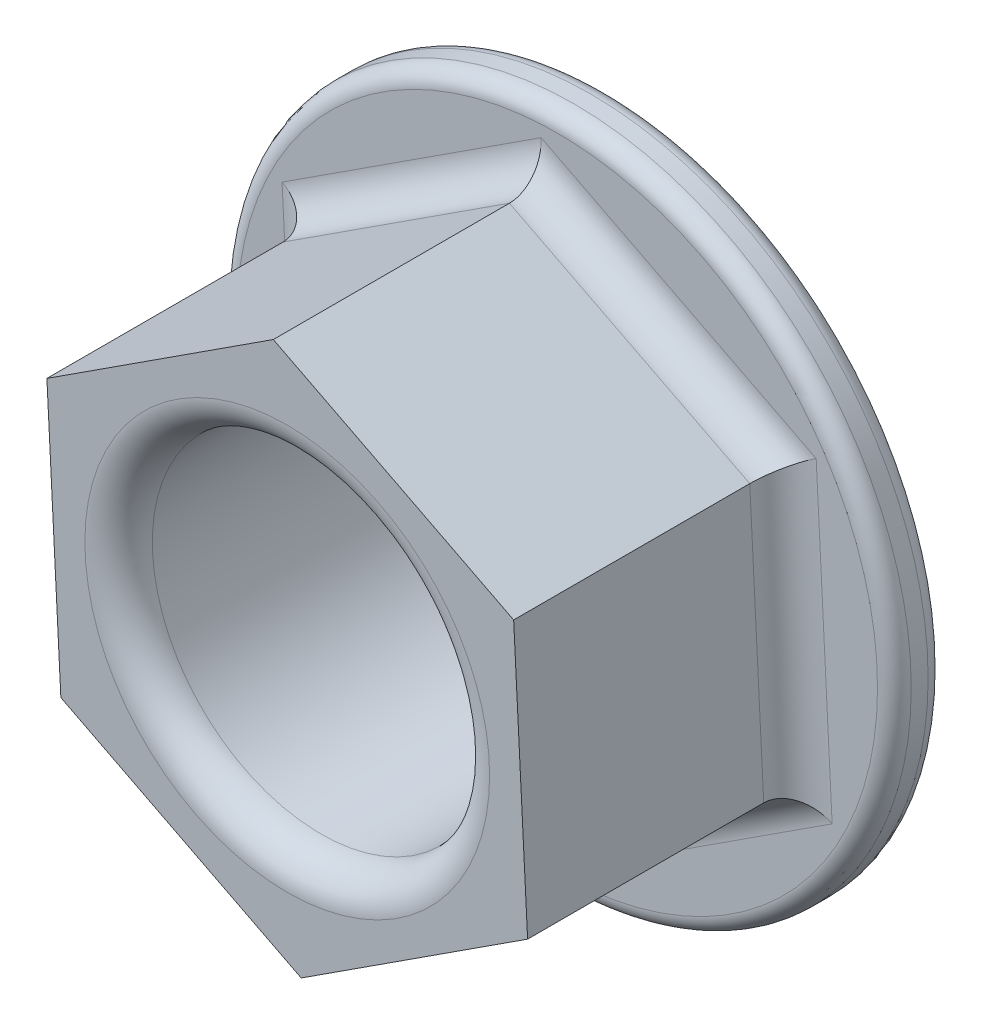
SolidWorks part; units mm, degrees
ref_plane "Front Plane" through (0, 0, 0) normal (0, 0, 1) x (1, 0, 0)
ref_plane "Top Plane" through (0, 0, 0) normal (0, 1, 0) x (1, 0, 0)
ref_plane "Right Plane" through (0, 0, 0) normal (1, 0, 0) x (0, 0, -1)
sketch "Sketch1" plane through (0, 0, 0) normal (0, 0, 1) x (1, 0, 0)
  circle A0 centre (0, 0) radius 10
  dimension "D1" = 20
extrude "Boss-Extrude2" add sketch "Sketch1" along normal blind 1.5
fillet "Fillet1" radius 0.5 2 edges at (10, 0, 0) (10, 0, 1.5)
sketch "Sketch3" plane through (0, 0, 1.5) normal (0, 0, 1) x (1, 0, 0)
  line L1 (-7.1259, 3.6362) -> (-6.712, -4.3531)
  line L2 (-6.712, -4.3531) -> (0.4139, -7.9893)
  line L3 (0.4139, -7.9893) -> (7.1259, -3.6362)
  line L4 (7.1259, -3.6362) -> (6.712, 4.3531)
  line L5 (6.712, 4.3531) -> (-0.4139, 7.9893)
  line L6 (-0.4139, 7.9893) -> (-7.1259, 3.6362)
  circle A0 centre (0, 0) radius 6.9282 construction
  dimension "D1" = 8
extrude "Boss-Extrude3" add sketch "Sketch3" along normal blind 8
fillet "Fillet2" radius 1 6 edges at (-3.149, -6.1712, 1.5) (-6.9189, -0.3585, 1.5) (-3.7699, 5.8127, 1.5) (3.149, 6.1712, 1.5) (6.9189, 0.3585, 1.5) (3.7699, -5.8127, 1.5)
sketch "Sketch5" plane through (0, 0, 9.5) normal (0, 0, 1) x (1, 0, 0)
  circle A0 centre (0, 0) radius 5
  dimension "D1" = 10
extrude "Cut-Extrude1" cut sketch "Sketch5" against normal through all contours A0
sketch "Sketch6" plane through (0, 0, 9.5) normal (0, 0, 1) x (1, 0, 0)
  circle A0 centre (0, 0) radius 5 construction
  circle A1 centre (0, 0) radius 5
curve "Helix/Spiral1" pitch 0.5 height 10 turns 20
sketch3d "3DSketch1"
  circle A0 centre (4.0448, -2.9388, -0.3) radius 0.0335
  spline S0 degree 3 poles (-5, 0, 9.5) (-5, 0.6503, 9.4897) (-4.7397, 1.9651, 9.4687) (-3.6276, 3.6271, 9.4375) (-1.9632, 4.7398, 9.4062) (0, 5.1301, 9.375) (1.9632, 4.7397, 9.3437) (3.6276, 3.6276, 9.3125) (4.7397, 1.9632, 9.2812) (5.1302, 0, 9.25) (4.7397, -1.9632, 9.2187) (3.6276, -3.6276, 9.1875) (1.9632, -4.7397, 9.1562) (0, -5.1302, 9.125) (-1.9632, -4.7397, 9.0937) (-3.6276, -3.6276, 9.0625) (-4.7397, -1.9632, 9.0312) (-5.1302, 0, 9) (-4.7397, 1.9632, 8.9687) (-3.6276, 3.6276, 8.9375) (-1.9632, 4.7397, 8.9062) (0, 5.1302, 8.875) (1.9632, 4.7397, 8.8438) (3.6276, 3.6276, 8.8125) (4.7397, 1.9632, 8.7812) (5.1302, 0, 8.75) (4.7397, -1.9632, 8.7187) (3.6276, -3.6276, 8.6875) (1.9632, -4.7397, 8.6562) (0, -5.1302, 8.625) (-1.9632, -4.7397, 8.5937) (-3.6276, -3.6276, 8.5625) (-4.7397, -1.9632, 8.5312) (-5.1302, 0, 8.5) (-4.7397, 1.9632, 8.4687) (-3.6276, 3.6276, 8.4375) (-1.9632, 4.7397, 8.4062) (0, 5.1302, 8.375) (1.9632, 4.7397, 8.3438) (3.6276, 3.6276, 8.3125) (4.7397, 1.9632, 8.2812) (5.1302, 0, 8.25) (4.7397, -1.9632, 8.2187) (3.6276, -3.6276, 8.1875) (1.9632, -4.7397, 8.1562) (0, -5.1302, 8.125) (-1.9632, -4.7397, 8.0937) (-3.6276, -3.6276, 8.0625) (-4.7397, -1.9632, 8.0312) (-5.1302, 0, 8) (-4.7397, 1.9632, 7.9687) (-3.6276, 3.6276, 7.9375) (-1.9632, 4.7397, 7.9062) (0, 5.1302, 7.875) (1.9632, 4.7397, 7.8438) (3.6276, 3.6276, 7.8125) (4.7397, 1.9632, 7.7812) (5.1302, 0, 7.75) (4.7397, -1.9632, 7.7188) (3.6276, -3.6276, 7.6875) (1.9632, -4.7397, 7.6562) (0, -5.1302, 7.625) (-1.9632, -4.7397, 7.5937) (-3.6276, -3.6276, 7.5625) (-4.7397, -1.9632, 7.5312) (-5.1302, 0, 7.5) (-4.7397, 1.9632, 7.4687) (-3.6276, 3.6276, 7.4375) (-1.9632, 4.7397, 7.4062) (0, 5.1302, 7.375) (1.9632, 4.7397, 7.3437) (3.6276, 3.6276, 7.3125) (4.7397, 1.9632, 7.2812) (5.1302, 0, 7.25) (4.7397, -1.9632, 7.2187) (3.6276, -3.6276, 7.1875) (1.9632, -4.7397, 7.1562) (0, -5.1302, 7.125) (-1.9632, -4.7397, 7.0937) (-3.6276, -3.6276, 7.0625) (-4.7397, -1.9632, 7.0312) (-5.1302, 0, 7) (-4.7397, 1.9632, 6.9687) (-3.6276, 3.6276, 6.9375) (-1.9632, 4.7397, 6.9062) (0, 5.1302, 6.875) (1.9632, 4.7397, 6.8437) (3.6276, 3.6276, 6.8125) (4.7397, 1.9632, 6.7812) (5.1302, 0, 6.75) (4.7397, -1.9632, 6.7187) (3.6276, -3.6276, 6.6875) (1.9632, -4.7397, 6.6562) (0, -5.1302, 6.625) (-1.9632, -4.7397, 6.5937) (-3.6276, -3.6276, 6.5625) (-4.7397, -1.9632, 6.5312) (-5.1302, 0, 6.5) (-4.7397, 1.9632, 6.4687) (-3.6276, 3.6276, 6.4375) (-1.9632, 4.7397, 6.4062) (0, 5.1302, 6.375) (1.9632, 4.7397, 6.3437) (3.6276, 3.6276, 6.3125) (4.7397, 1.9632, 6.2812) (5.1302, 0, 6.25) (4.7397, -1.9632, 6.2187) (3.6276, -3.6276, 6.1875) (1.9632, -4.7397, 6.1562) (0, -5.1302, 6.125) (-1.9632, -4.7397, 6.0937) (-3.6276, -3.6276, 6.0625) (-4.7397, -1.9632, 6.0312) (-5.1302, 0, 6) (-4.7397, 1.9632, 5.9687) (-3.6276, 3.6276, 5.9375) (-1.9632, 4.7397, 5.9062) (0, 5.1302, 5.875) (1.9632, 4.7397, 5.8437) (3.6276, 3.6276, 5.8125) (4.7397, 1.9632, 5.7812) (5.1302, 0, 5.75) (4.7397, -1.9632, 5.7187) (3.6276, -3.6276, 5.6875) (1.9632, -4.7397, 5.6562) (0, -5.1302, 5.625) (-1.9632, -4.7397, 5.5937) (-3.6276, -3.6276, 5.5625) (-4.7397, -1.9632, 5.5312) (-5.1302, 0, 5.5) (-4.7397, 1.9632, 5.4687) (-3.6276, 3.6276, 5.4375) (-1.9632, 4.7397, 5.4062) (0, 5.1302, 5.375) (1.9632, 4.7397, 5.3437) (3.6276, 3.6276, 5.3125) (4.7397, 1.9632, 5.2812) (5.1302, 0, 5.25) (4.7397, -1.9632, 5.2187) (3.6276, -3.6276, 5.1875) (1.9632, -4.7397, 5.1562) (0, -5.1302, 5.125) (-1.9632, -4.7397, 5.0937) (-3.6276, -3.6276, 5.0625) (-4.7397, -1.9632, 5.0312) (-5.1302, 0, 5) (-4.7397, 1.9632, 4.9687) (-3.6276, 3.6276, 4.9375) (-1.9632, 4.7397, 4.9062) (0, 5.1302, 4.875) (1.9632, 4.7397, 4.8437) (3.6276, 3.6276, 4.8125) (4.7397, 1.9632, 4.7812) (5.1302, 0, 4.75) (4.7397, -1.9632, 4.7187) (3.6276, -3.6276, 4.6875) (1.9632, -4.7397, 4.6562) (0, -5.1302, 4.625) (-1.9632, -4.7397, 4.5937) (-3.6276, -3.6276, 4.5625) (-4.7397, -1.9632, 4.5312) (-5.1302, 0, 4.5) (-4.7397, 1.9632, 4.4687) (-3.6276, 3.6276, 4.4375) (-1.9632, 4.7397, 4.4062) (0, 5.1302, 4.375) (1.9632, 4.7397, 4.3437) (3.6276, 3.6276, 4.3125) (4.7397, 1.9632, 4.2812) (5.1302, 0, 4.25) (4.7397, -1.9632, 4.2187) (3.6276, -3.6276, 4.1875) (1.9632, -4.7397, 4.1562) (0, -5.1302, 4.125) (-1.9632, -4.7397, 4.0937) (-3.6276, -3.6276, 4.0625) (-4.7397, -1.9632, 4.0312) (-5.1302, 0, 4) (-4.7397, 1.9632, 3.9687) (-3.6276, 3.6276, 3.9375) (-1.9632, 4.7397, 3.9062) (0, 5.1302, 3.875) (1.9632, 4.7397, 3.8437) (3.6276, 3.6276, 3.8125) (4.7397, 1.9632, 3.7812) (5.1302, 0, 3.75) (4.7397, -1.9632, 3.7187) (3.6276, -3.6276, 3.6875) (1.9632, -4.7397, 3.6562) (0, -5.1302, 3.625) (-1.9632, -4.7397, 3.5937) (-3.6276, -3.6276, 3.5625) (-4.7397, -1.9632, 3.5312) (-5.1302, 0, 3.5) (-4.7397, 1.9632, 3.4687) (-3.6276, 3.6276, 3.4375) (-1.9632, 4.7397, 3.4062) (0, 5.1302, 3.375) (1.9632, 4.7397, 3.3437) (3.6276, 3.6276, 3.3125) (4.7397, 1.9632, 3.2812) (5.1302, 0, 3.25) (4.7397, -1.9632, 3.2187) (3.6276, -3.6276, 3.1875) (1.9632, -4.7397, 3.1562) (0, -5.1302, 3.125) (-1.9632, -4.7397, 3.0937) (-3.6276, -3.6276, 3.0625) (-4.7397, -1.9632, 3.0312) (-5.1302, 0, 3) (-4.7397, 1.9632, 2.9687) (-3.6276, 3.6276, 2.9375) (-1.9632, 4.7397, 2.9062) (0, 5.1302, 2.875) (1.9632, 4.7397, 2.8437) (3.6276, 3.6276, 2.8125) (4.7397, 1.9632, 2.7812) (5.1302, 0, 2.75) (4.7397, -1.9632, 2.7187) (3.6276, -3.6276, 2.6875) (1.9632, -4.7397, 2.6562) (0, -5.1302, 2.625) (-1.9632, -4.7397, 2.5937) (-3.6276, -3.6276, 2.5625) (-4.7397, -1.9632, 2.5312) (-5.1302, 0, 2.5) (-4.7397, 1.9632, 2.4687) (-3.6276, 3.6276, 2.4375) (-1.9632, 4.7397, 2.4062) (0, 5.1302, 2.375) (1.9632, 4.7397, 2.3437) (3.6276, 3.6276, 2.3125) (4.7397, 1.9632, 2.2812) (5.1302, 0, 2.25) (4.7397, -1.9632, 2.2187) (3.6276, -3.6276, 2.1875) (1.9632, -4.7397, 2.1562) (0, -5.1302, 2.125) (-1.9632, -4.7397, 2.0937) (-3.6276, -3.6276, 2.0625) (-4.7397, -1.9632, 2.0312) (-5.1302, 0, 2) (-4.7397, 1.9632, 1.9687) (-3.6276, 3.6276, 1.9375) (-1.9632, 4.7397, 1.9062) (0, 5.1302, 1.875) (1.9632, 4.7397, 1.8437) (3.6276, 3.6276, 1.8125) (4.7397, 1.9632, 1.7812) (5.1302, 0, 1.75) (4.7397, -1.9632, 1.7187) (3.6276, -3.6276, 1.6875) (1.9632, -4.7397, 1.6562) (0, -5.1302, 1.625) (-1.9632, -4.7397, 1.5937) (-3.6276, -3.6276, 1.5625) (-4.7397, -1.9632, 1.5312) (-5.1302, 0, 1.5) (-4.7397, 1.9632, 1.4687) (-3.6276, 3.6276, 1.4375) (-1.9632, 4.7397, 1.4062) (0, 5.1302, 1.375) (1.9632, 4.7397, 1.3437) (3.6276, 3.6276, 1.3125) (4.7397, 1.9632, 1.2812) (5.1302, 0, 1.25) (4.7397, -1.9632, 1.2187) (3.6276, -3.6276, 1.1875) (1.9632, -4.7397, 1.1562) (0, -5.1302, 1.125) (-1.9632, -4.7397, 1.0937) (-3.6276, -3.6276, 1.0625) (-4.7397, -1.9632, 1.0312) (-5.1302, 0, 1) (-4.7397, 1.9632, 0.9687) (-3.6276, 3.6276, 0.9375) (-1.9632, 4.7397, 0.9062) (0, 5.1302, 0.875) (1.9632, 4.7397, 0.8437) (3.6276, 3.6276, 0.8125) (4.7397, 1.9632, 0.7812) (5.1302, 0, 0.75) (4.7397, -1.9632, 0.7187) (3.6276, -3.6276, 0.6875) (1.9632, -4.7397, 0.6562) (0, -5.1302, 0.625) (-1.9632, -4.7397, 0.5937) (-3.6276, -3.6276, 0.5625) (-4.7397, -1.9632, 0.5312) (-5.1302, 0, 0.5) (-4.7397, 1.9632, 0.4687) (-3.6276, 3.6276, 0.4375) (-1.9632, 4.7397, 0.4062) (0, 5.1302, 0.375) (1.9632, 4.7397, 0.3437) (3.6276, 3.6276, 0.3125) (4.7397, 1.9632, 0.2812) (5.1302, 0, 0.25) (4.7397, -1.9632, 0.2187) (3.6276, -3.6276, 0.1875) (1.9632, -4.7397, 0.1562) (0, -5.1302, 0.125) (-1.9632, -4.7397, 0.0937) (-3.6276, -3.6276, 0.0625) (-4.7397, -1.9632, 0.0313) (-5.1302, 0, 0) (-4.7397, 1.9632, -0.0312) (-3.6276, 3.6276, -0.0625) (-1.9632, 4.7397, -0.0937) (0, 5.1302, -0.125) (1.9632, 4.7397, -0.1562) (3.6276, 3.6276, -0.1875) (4.7397, 1.9632, -0.2187) (5.1302, 0, -0.25) (4.7397, -1.9632, -0.2812) (3.6276, -3.6276, -0.3125) (1.9632, -4.7397, -0.3437) (0, -5.1301, -0.375) (-1.9632, -4.7398, -0.4062) (-3.6276, -3.6271, -0.4375) (-4.7397, -1.9651, -0.4687) (-5, -0.6503, -0.4897) (-5, 0, -0.5) knots 0 0 0 0 0.003125 0.00625 0.009375 0.0125 0.015625 0.01875 0.021875 0.025 0.028125 0.03125 0.034375 0.0375 0.040625 0.04375 0.046875 0.05 0.053125 0.05625 0.059375 0.0625 0.065625 0.06875 0.071875 0.075 0.078125 0.08125 0.084375 0.0875 0.090625 0.09375 0.096875 0.1 0.103125 0.10625 0.109375 0.1125 0.115625 0.11875 0.121875 0.125 0.128125 0.13125 0.134375 0.1375 0.140625 0.14375 0.146875 0.15 0.153125 0.15625 0.159375 0.1625 0.165625 0.16875 0.171875 0.175 0.178125 0.18125 0.184375 0.1875 0.190625 0.19375 0.196875 0.2 0.203125 0.20625 0.209375 0.2125 0.215625 0.21875 0.221875 0.225 0.228125 0.23125 0.234375 0.2375 0.240625 0.24375 0.246875 0.25 0.253125 0.25625 0.259375 0.2625 0.265625 0.26875 0.271875 0.275 0.278125 0.28125 0.284375 0.2875 0.290625 0.29375 0.296875 0.3 0.303125 0.30625 0.309375 0.3125 0.315625 0.31875 0.321875 0.325 0.328125 0.33125 0.334375 0.3375 0.340625 0.34375 0.346875 0.35 0.353125 0.35625 0.359375 0.3625 0.365625 0.36875 0.371875 0.375 0.378125 0.38125 0.384375 0.3875 0.390625 0.39375 0.396875 0.4 0.403125 0.40625 0.409375 0.4125 0.415625 0.41875 0.421875 0.425 0.428125 0.43125 0.434375 0.4375 0.440625 0.44375 0.446875 0.45 0.453125 0.45625 0.459375 0.4625 0.465625 0.46875 0.471875 0.475 0.478125 0.48125 0.484375 0.4875 0.490625 0.49375 0.496875 0.5 0.503125 0.50625 0.509375 0.5125 0.515625 0.51875 0.521875 0.525 0.528125 0.53125 0.534375 0.5375 0.540625 0.54375 0.546875 0.55 0.553125 0.55625 0.559375 0.5625 0.565625 0.56875 0.571875 0.575 0.578125 0.58125 0.584375 0.5875 0.590625 0.59375 0.596875 0.6 0.603125 0.60625 0.609375 0.6125 0.615625 0.61875 0.621875 0.625 0.628125 0.63125 0.634375 0.6375 0.640625 0.64375 0.646875 0.65 0.653125 0.65625 0.659375 0.6625 0.665625 0.66875 0.671875 0.675 0.678125 0.68125 0.684375 0.6875 0.690625 0.69375 0.696875 0.7 0.703125 0.70625 0.709375 0.7125 0.715625 0.71875 0.721875 0.725 0.728125 0.73125 0.734375 0.7375 0.740625 0.74375 0.746875 0.75 0.753125 0.75625 0.759375 0.7625 0.765625 0.76875 0.771875 0.775 0.778125 0.78125 0.784375 0.7875 0.790625 0.79375 0.796875 0.8 0.803125 0.80625 0.809375 0.8125 0.815625 0.81875 0.821875 0.825 0.828125 0.83125 0.834375 0.8375 0.840625 0.84375 0.846875 0.85 0.853125 0.85625 0.859375 0.8625 0.865625 0.86875 0.871875 0.875 0.878125 0.88125 0.884375 0.8875 0.890625 0.89375 0.896875 0.9 0.903125 0.90625 0.909375 0.9125 0.915625 0.91875 0.921875 0.925 0.928125 0.93125 0.934375 0.9375 0.940625 0.94375 0.946875 0.95 0.953125 0.95625 0.959375 0.9625 0.965625 0.96875 0.971875 0.975 0.978125 0.98125 0.984375 0.9875 0.990625 0.99375 0.996875 1 1 1 1 construction
  point P2 (4.0783, -2.9388, -0.3)
  dimension "D1" = 0.3
sweep "Cut-Sweep1" [suppressed] cut profiles "3DSketch1" path "Helix/Spiral1"
fillet "Fillet3" radius 1 2 edges at (5, 0, 9.5) (5, 0, 0)
